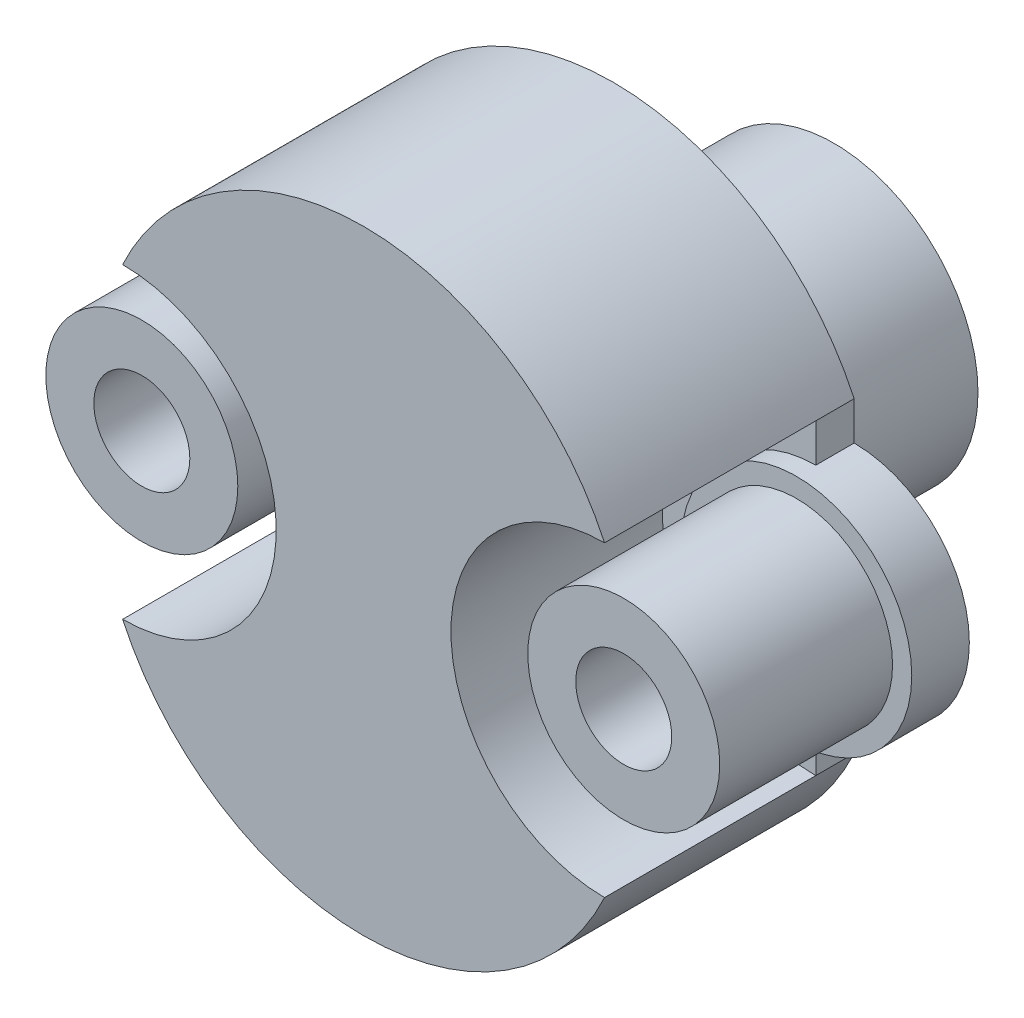
SolidWorks part; units mm, degrees
ref_plane "Płaszczyzna przednia" through (0, 0, 0) normal (0, 0, 1) x (1, 0, 0)
ref_plane "Płaszczyzna górna" through (0, 0, 0) normal (0, 1, 0) x (1, 0, 0)
ref_plane "Płaszczyzna prawa" through (0, 0, 0) normal (1, 0, 0) x (0, 0, -1)
sketch "Szkic1" plane through (0, 0, 0) normal (0, 0, 1) x (1, 0, 0)
  arc A7 (12.55, -8) -> (12.55, 8) centre (12.55, 0) ccw
  arc A8 (-12.55, 8) -> (-12.55, -8) centre (-12.55, 0) ccw
  arc A9 (-12.55, 8) -> (12.55, 8) centre (0, 2.1561) cw
  arc A10 (-12.55, -8) -> (12.55, -8) centre (0, -2.1561) ccw
  point P14 (0, 16)
  point P15 (0, -16)
  dimension "D3" = 8
  dimension "D7" = 8
  dimension "D9" = 16
  dimension "D2" = 12.55
  dimension "D4" = 12.55
  dimension "D5" = 0
  dimension "D6" = 0
  dimension "D10" = 16
extrude "Dodanie-wyciągnięcie1" add sketch "Szkic1" along normal blind 3
sketch "Szkic2" plane through (0, 0, 3) normal (0, 0, 1) x (1, 0, 0)
  circle A0 centre (12.55, 0) radius 5
  circle A1 centre (-12.55, 0) radius 5
  dimension "D1" = 10
  dimension "D2" = 10
extrude "Dodanie-wyciągnięcie2" add sketch "Szkic2" along normal blind 9
sketch "Szkic3" plane through (0, 0, 12) normal (0, 0, 1) x (1, 0, 0)
  circle A0 centre (12.55, 0) radius 2.5
  circle A1 centre (-12.55, 0) radius 2.5
  dimension "D1" = 5
  dimension "D2" = 5
extrude "Wytnij-wyciągnięcie1" cut sketch "Szkic3" against normal up to next
sketch "Szkic4" plane through (0, 0, 3) normal (0, 0, 1) x (1, 0, 0)
  arc A0 (-12.55, -8) -> (-12.55, 8) centre (-12.55, 0) ccw
  arc A1 (12.55, 8) -> (12.55, -8) centre (12.55, 0) ccw
  arc A2 (-12.55, 8) -> (12.55, 8) centre (0, 2.1561) cw
  arc A3 (-12.55, -8) -> (12.55, -8) centre (0, -2.1561) ccw
  dimension "D1" = 13.8439
  dimension "D2" = 13.8439
extrude "Dodanie-wyciągnięcie3" add sketch "Szkic4" along normal blind 10
sketch "Szkic5" plane through (0, 0, 0) normal (0, 0, -1) x (-1, 0, 0)
  circle A0 centre (0, 0) radius 7.5
  dimension "D1" = 15
extrude "Dodanie-wyciągnięcie4" add sketch "Szkic5" along normal blind 11.5
fillet "Zaokrąglenie1" radius 5 1 edges at (-7.5, 0, 0)
sketch "Szkic6" plane through (0, 0, -11.5) normal (0, 0, -1) x (-1, 0, 0)
  line L1 (-2.55, -2.55) -> (2.55, -2.55)
  line L2 (-2.55, -2.55) -> (-2.55, 2.55)
  line L3 (-2.55, 2.55) -> (2.55, 2.55)
  line L4 (2.55, -2.55) -> (2.55, 2.55)
  line L5 (-2.55, -2.55) -> (2.55, 2.55) construction
  line L6 (-2.55, 2.55) -> (2.55, -2.55) construction
  point P0 (0, 0)
  dimension "D1" = 5.1
  dimension "D2" = 5.1
extrude "Wytnij-wyciągnięcie2" cut sketch "Szkic6" against normal blind 7
sketch "Szkic8" plane through (0, 0, 3) normal (0, 0, 1) x (1, 0, 0)
  circle A0 centre (-12.55, 0) radius 6
  circle A1 centre (-12.55, 0) radius 8
  circle A2 centre (12.55, 0) radius 6
  circle A3 centre (12.55, 0) radius 8
  dimension "D1" = 12
  dimension "D2" = 12
  dimension "D3" = 16
  dimension "D4" = 16
extrude "Wytnij-wyciągnięcie3" cut sketch "Szkic8" against normal blind 1
sketch "Szkic9" plane through (0, 0, 2) normal (0, 0, 1) x (1, 0, 0)
  line L0 (12.55, 8) -> (12.55, 6)
  line L1 (12.55, -6) -> (12.55, -8)
  line L2 (-12.55, 8) -> (-12.55, 6)
  line L3 (-12.55, -6) -> (-12.55, -8)
  arc A0 (12.55, -6) -> (12.55, 6) centre (12.55, 0) ccw
  arc A1 (12.55, -8) -> (12.55, 8) centre (12.55, 0) ccw
  arc A2 (-12.55, 6) -> (-12.55, -6) centre (-12.55, 0) ccw
  arc A3 (-12.55, 8) -> (-12.55, -8) centre (-12.55, 0) ccw
  dimension "D1" = 12
  dimension "D3" = 12
extrude "Wytnij-wyciągnięcie4" cut sketch "Szkic9" against normal up to next
